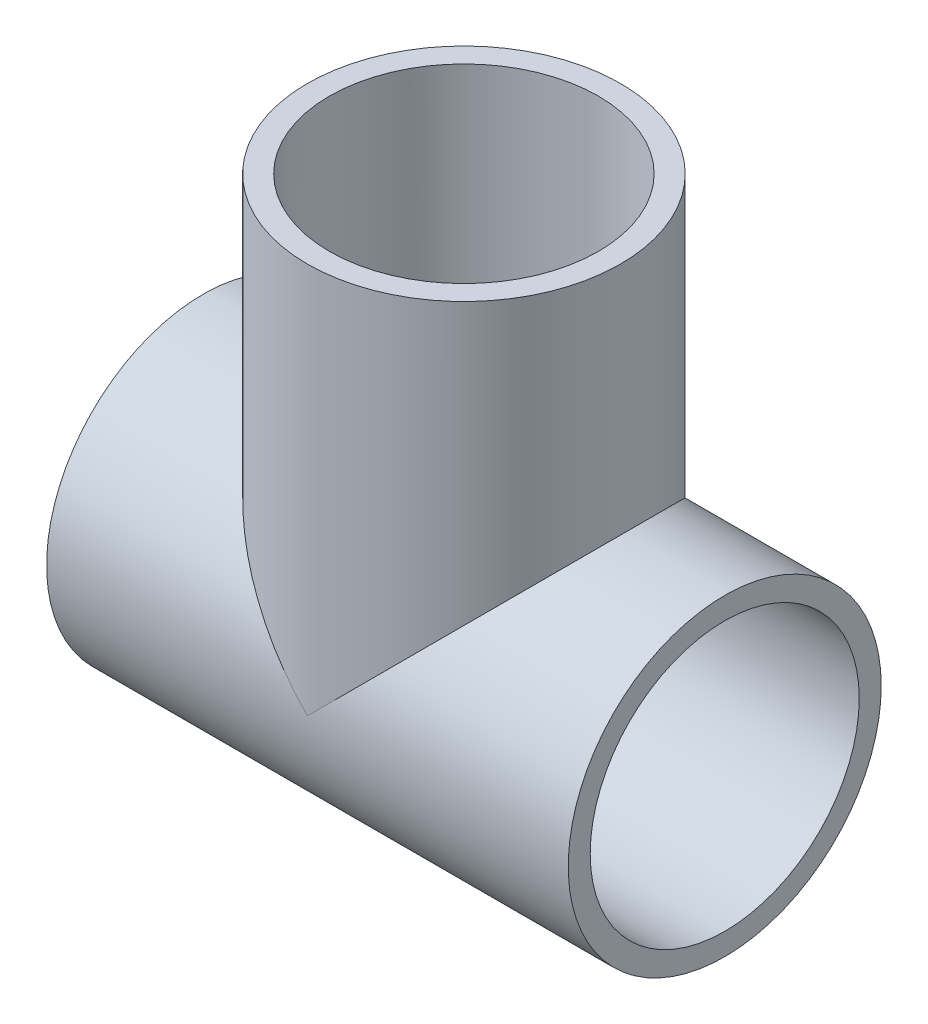
SolidWorks part; units mm, degrees
material "Nylon 101"
ref_plane "Front Plane" through (0, 0, 0) normal (0, 0, 1) x (1, 0, 0)
ref_plane "Top Plane" through (0, 0, 0) normal (0, 1, 0) x (1, 0, 0)
ref_plane "Right Plane" through (0, 0, 0) normal (1, 0, 0) x (0, 0, -1)
sketch "Sketch1" plane through (0, 0, 0) normal (1, 0, 0) x (0, 0, -1)
  circle A0 centre (0, 0) radius 7.62
  dimension "D2" = 15.24
extrude "Boss-Extrude1" add sketch "Sketch1" along normal blind 25.4
sketch "Sketch2" plane through (0, 0, 0) normal (0, 1, 0) x (1, 0, 0)
  circle A1 centre (12.7, 0) radius 7.62
  dimension "D3" = 15.24
  dimension "D1" = 12.7
extrude "Boss-Extrude2" add sketch "Sketch2" along normal blind 19.05
sketch "Sketch3" plane through (25.4, 0, 0) normal (1, 0, 0) x (0, 0, -1)
  circle A0 centre (0, 0) radius 6.55
  dimension "D1" = 13.1
extrude "Cut-Extrude1" cut sketch "Sketch3" against normal through all
sketch "Sketch4" plane through (0, 19.05, 0) normal (0, 1, 0) x (1, 0, 0)
  circle A0 centre (12.7, 0) radius 6.55
  dimension "D1" = 13.1
extrude "Cut-Extrude2" cut sketch "Sketch4" against normal up to next
